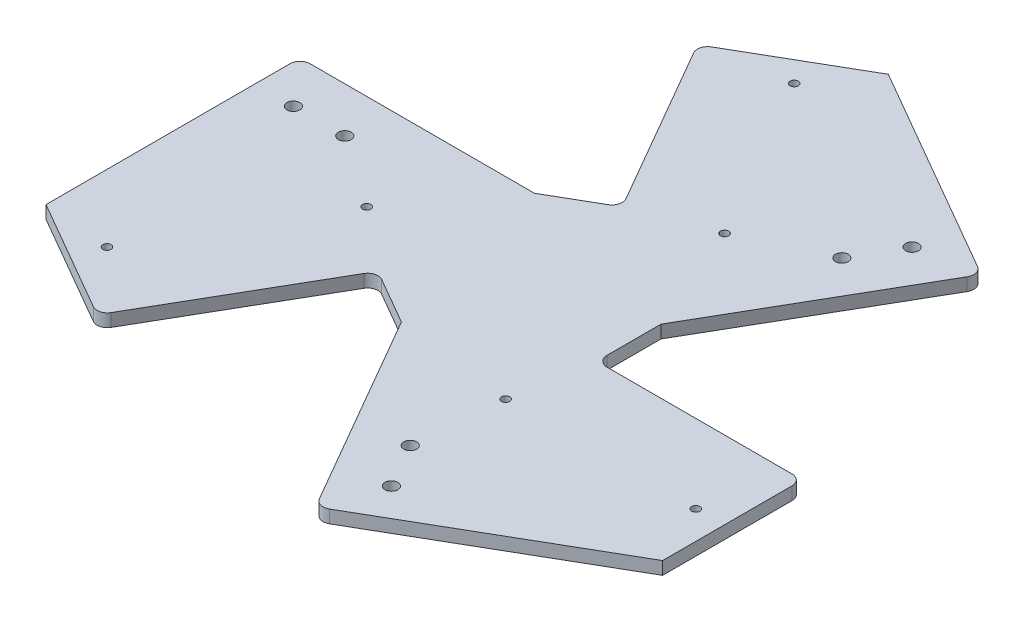
SolidWorks part; units mm, degrees
ref_plane "Front Plane" through (0, 0, 0) normal (0, 0, 1) x (1, 0, 0)
ref_plane "Top Plane" through (0, 0, 0) normal (0, 1, 0) x (1, 0, 0)
ref_plane "Right Plane" through (0, 0, 0) normal (1, 0, 0) x (0, 0, -1)
sketch "Sketch1" plane through (0, 0, 0) normal (0, 1, 0) x (1, 0, 0)
  line L0 (76.2, -43.9941) -> (76.2, 0) construction
  line L1 (76.2, -43.9941) -> (24.0268, -74.1163)
  line L2 (-18.2543, 18.7903) -> (-73.66, 18.7903)
  line L3 (-7.1457, -25.2038) -> (20.5571, -73.1866)
  line L4 (-76.2, -43.9941) -> (-76.2, 16.2503)
  line L5 (-76.2, -43.9941) -> (-38.1, -65.9911) construction
  line L6 (13.2547, -38.1978) -> (25013.2547, -43339.4679) construction
  line L7 (25.4, 6.4135) -> (25.4, -6.9215)
  line L8 (27.94, -9.4615) -> (73.66, -9.4615)
  line L9 (76.2, -12.0015) -> (76.2, -43.9941)
  line L10 (25.4, 6.4135) -> (53.1029, 54.3963)
  line L11 (-48.4936, -59.9904) -> (-76.2, -43.9941)
  line L12 (-22.1639, -19.466) -> (-45.0239, -59.0607)
  line L13 (0, 87.9882) -> (52.1732, 57.866)
  line L14 (-7.1457, -25.2038) -> (-18.6942, -18.5363)
  line L16 (0, 87.9882) -> (-38.1, 65.9911) construction
  line L17 (-27.7064, 71.9919) -> (0, 87.9882)
  line L18 (-5.7761, 28.9275) -> (-28.6361, 68.5222)
  line L20 (-18.2543, 18.7903) -> (-6.7058, 25.4578)
  line L21 (0, 0) -> (-49999.9986, 0) construction
  line L22 (0, 0) -> (-25000, 43301.2702) construction
  line L23 (0, 0) -> (-25000, -43301.2702) construction
  line L24 (25.4, 0) -> (76.2, 0) construction
  line L25 (-12.7, -21.997) -> (-38.1, -65.9911) construction
  line L26 (-12.7, 21.997) -> (-38.1, 65.9911) construction
  line L27 (76.2, 8.001) -> (76.2, 45.974) [skipped]
  line L28 (-31.1709, -69.9916) -> (1.7147, -88.9781) [skipped]
  line L29 (-45.0291, 61.9906) -> (-77.9147, 43.0041) [skipped]
  line L30 (-32.5457, -69.1979) -> (-7.1457, -25.2038) [skipped]
  line L31 (-43.6543, 62.7844) -> (-18.2543, 18.7903) [skipped]
  line L32 (76.2, 6.4135) -> (25.4, 6.4135) [skipped]
  circle A0 centre (69.2404, -28.829) radius 1.016
  circle A1 centre (0, 0) radius 76.2 construction
  circle A2 centre (-59.5868, -45.5494) radius 1.016
  circle A3 centre (-9.6536, 74.3784) radius 1.016
  circle A4 centre (22.2504, -28.829) radius 1.016
  circle A5 centre (-36.0918, -4.8549) radius 1.016
  circle A6 centre (13.8414, 33.6839) radius 1.016
  circle A7 centre (26.7384, -61.5522) radius 1.5875
  circle A8 centre (20.3884, -50.5537) radius 1.5875
  circle A9 centre (-53.975, 7.62) radius 1.5875
  circle A10 centre (-66.675, 7.62) radius 1.5875
  circle A11 centre (33.5866, 42.9337) radius 1.5875
  circle A12 centre (39.9366, 53.9322) radius 1.5875
  arc A13 (24.0268, -74.1163) -> (20.5571, -73.1866) centre (22.7568, -71.9166) cw
  arc A14 (73.66, -9.4615) -> (76.2, -12.0015) centre (73.66, -12.0015) cw
  arc A15 (53.1029, 54.3963) -> (52.1732, 57.866) centre (50.9032, 55.6663) ccw
  arc A16 (-27.7064, 71.9919) -> (-28.6361, 68.5222) centre (-26.4364, 69.7922) ccw
  arc A17 (-48.4936, -59.9904) -> (-45.0239, -59.0607) centre (-47.2236, -57.7907) ccw
  arc A18 (-73.66, 18.7903) -> (-76.2, 16.2503) centre (-73.66, 16.2503) ccw
  arc A19 (-22.1639, -19.466) -> (-18.6942, -18.5363) centre (-19.9642, -20.736) cw
  arc A20 (25.4, -6.9215) -> (27.94, -9.4615) centre (27.94, -6.9215) ccw
  arc A21 (-5.7761, 28.9275) -> (-6.7058, 25.4578) centre (-7.9758, 27.6575) cw
  point P72 (76.2, -9.4615)
  point P85 (25.4, -9.4615)
  dimension "D2" = 15.875
  dimension "D6" = 152.4
  dimension "D13" = 2.032
  dimension "D17" = 2.032
  dimension "D21" = 3.175
  dimension "D22" = 3.175
  dimension "D25" = 2.54
  dimension "D1" = 120
  dimension "D3" = 50.8
  dimension "D4" = 3
  dimension "D5" = 3
  dimension "D7" = 9.4615
  dimension "D9" = 120
  dimension "D10" = 120
  dimension "D11" = 6.9596
  dimension "D12" = 19.3675
  dimension "D15" = 19.3675
  dimension "D16" = 53.9496
  dimension "D19" = 9.525
  dimension "D20" = 12.7
  dimension "D24" = 7.62
  dimension "D8" = 3
  dimension "D14" = 3
  dimension "D18" = 3
  dimension "D23" = 3
extrude "Boss-Extrude2" add sketch "Sketch1" along normal blind 3.175
